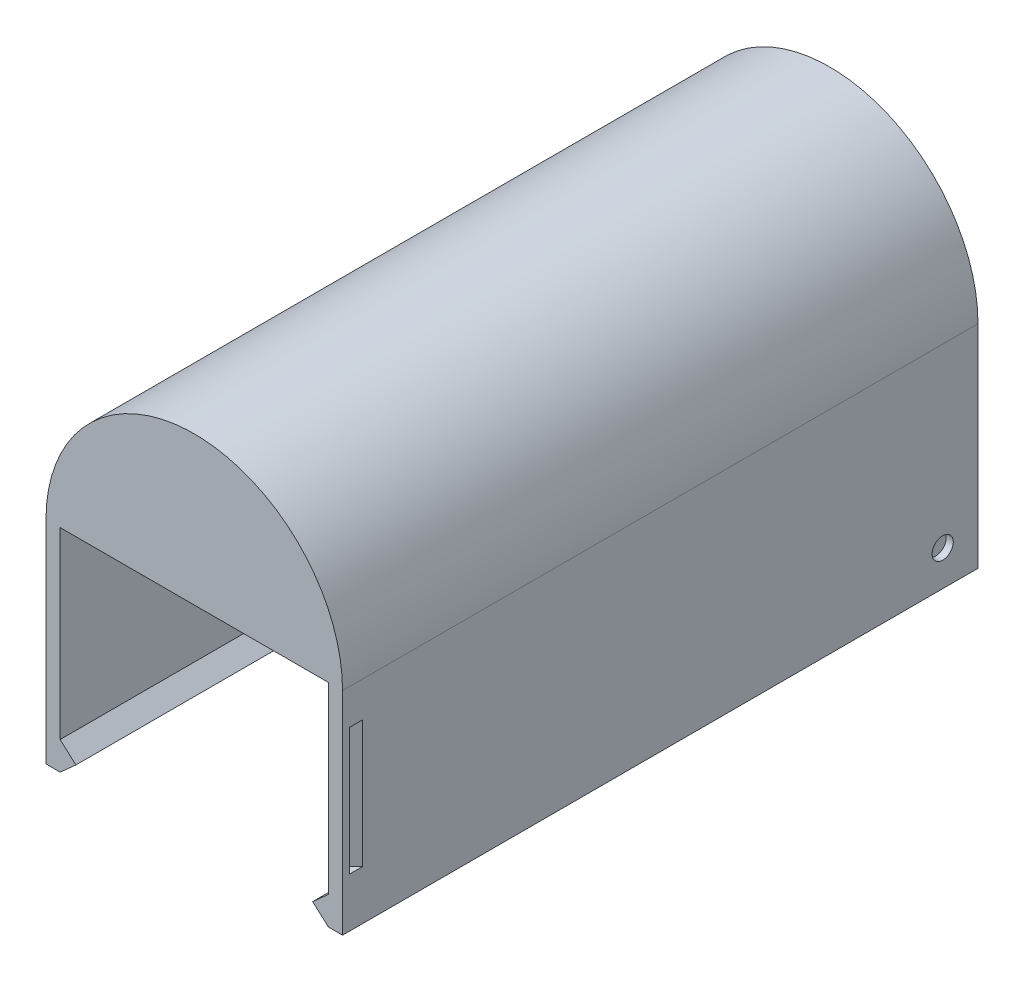
SolidWorks part; units mm, degrees
ref_plane "Front Plane" through (0, 0, 0) normal (0, 0, 1) x (1, 0, 0)
ref_plane "Top Plane" through (0, 0, 0) normal (0, 1, 0) x (1, 0, 0)
ref_plane "Right Plane" through (0, 0, 0) normal (1, 0, 0) x (0, 0, -1)
sketch "Sketch2" plane through (0, 0, 0) normal (0, 0, 1) x (1, 0, 0)
  line L0 (0, 0) -> (0, 30)
  line L1 (42, 0) -> (42, 30)
  line L2 (2, 0) -> (2, 30)
  line L3 (40, 0) -> (40, 30)
  line L4 (0, 0) -> (2, 0)
  line L5 (42, 0) -> (40, 0)
  arc A0 (42, 30) -> (0, 30) centre (21, 30) ccw
  arc A1 (40, 30) -> (2, 30) centre (21, 30) ccw
  dimension "D1" = 30
  dimension "D2" = 42
  dimension "D3" = 2
extrude "Boss-Extrude1" add sketch "Sketch2" along normal blind 90
sketch "Sketch3" plane through (0, 0, 90) normal (0, 0, 1) x (1, 0, 0)
  line L0 (2, 30) -> (40, 30)
  arc A0 (40, 30) -> (2, 30) centre (21, 30) ccw
extrude "Boss-Extrude2" add sketch "Sketch3" against normal blind 1
sketch "Sketch5" plane through (0, 0, 0) normal (-1, 0, 0) x (0, 0, 1)
  line L0 (20.5, 17.5) -> (24.5, 17.5) construction
  line L1 (20.5, 23) -> (24.5, 23)
  line L2 (20.5, 12) -> (24.5, 12)
  line L3 (0, 30) -> (0, 0) construction
  line L4 (90, 0) -> (0, 0) construction
  arc A0 (20.5, 23) -> (20.5, 12) centre (20.5, 17.5) ccw
  arc A1 (24.5, 12) -> (24.5, 23) centre (24.5, 17.5) ccw
  point P2 (22.5, 17.5)
  point P7 (30, 17.5)
  point P8 (15, 17.5)
  dimension "D1" = 15
  dimension "D2" = 12
  dimension "D3" = 11
  dimension "D4" = 15
extrude "Cut-Extrude2" cut sketch "Sketch5" against normal up to surface (2 mm away) up to face at (2, 18, 53.8)
sketch "Sketch6" plane through (0, 0, 0) normal (-1, 0, 0) x (0, 0, 1)
  line L0 (90, 0) -> (0, 0) construction
  line L1 (0, 30) -> (0, 0) construction
  circle A0 centre (5, 5) radius 1.5
  dimension "D2" = 3
  dimension "D1" = 5
  dimension "D3" = 5
extrude "Cut-Extrude3" cut sketch "Sketch6" against normal blind 1
ref_plane "Plane1" through (21, 0, 0) normal (1, 0, 0) x (0, 0, -1)
mirror "Mirror1" about plane through (21, 0, 0) normal (1, 0, 0) of "Cut-Extrude3"
ref_plane "Plane2" through (0, 7, 0) normal (0, -1, 0) x (-1, 0, 0)
sketch "Sketch7" plane through (0, 7, 0) normal (0, -1, 0) x (-1, 0, 0)
  line L0 (0.087, -90.0637) -> (0.087, -89.0637) construction
  line L1 (0.087, -89.0637) -> (0.087, -87.0637)
  line L2 (0.087, -87.0637) -> (-0.9118, -88.1139)
  line L3 (-0.9118, -88.1139) -> (0.087, -89.0637)
  dimension "D1" = 1
  dimension "D2" = 2
  dimension "D4" = 90
extrude "Cut-Extrude4" cut sketch "Sketch7" against normal blind 18
mirror "Mirror2" about plane through (21, 0, 0) normal (1, 0, 0) of "Cut-Extrude4"
sketch "Sketch8" plane through (0, 0, 90) normal (0, 0, 1) x (1, 0, 0)
  line L0 (2, 0) -> (4.2361, 2)
  line L2 (4.2361, 2) -> (2, 4)
  line L3 (2, 0) -> (2, 30) construction
  line L5 (2, 4) -> (2, 0)
  point P6 (3.9843, 1.75)
  dimension "D2" = 3
  dimension "D3" = 3
  dimension "D4" = 4
extrude "Boss-Extrude3" add sketch "Sketch8" against normal blind 78 contours L5 L0 L2
mirror "Mirror3" about plane through (21, 0, 0) normal (1, 0, 0) of "Boss-Extrude3"
sketch "Sketch9" plane through (0, 7, 0) normal (0, -1, 0) x (-1, 0, 0)
  line L0 (-2, -8) -> (-2, -14)
  line L1 (-2, -12) -> (-2, 0) construction
  line L2 (-2, -14) -> (-4.6458, -11)
  line L3 (-4.6458, -11) -> (-2, -8)
  line L4 (-2, -39) -> (-2, -45)
  line L5 (-2, -90) -> (-2, -12) construction
  line L6 (-2, -45) -> (-4.6458, -42)
  line L7 (-4.6458, -42) -> (-2, -39)
  line L8 (0, -15) -> (-2, -15) construction
  point P9 (-13.3183, -8.9868)
  dimension "D1" = 6
  dimension "D2" = 6
  dimension "D3" = 4
  dimension "D4" = 4
  dimension "D5" = 4
  dimension "D6" = 4
  dimension "D7" = 25
  dimension "D8" = 1
extrude "Boss-Extrude4" add sketch "Sketch9" against normal blind 6 from offset 8 offset against normal yes
